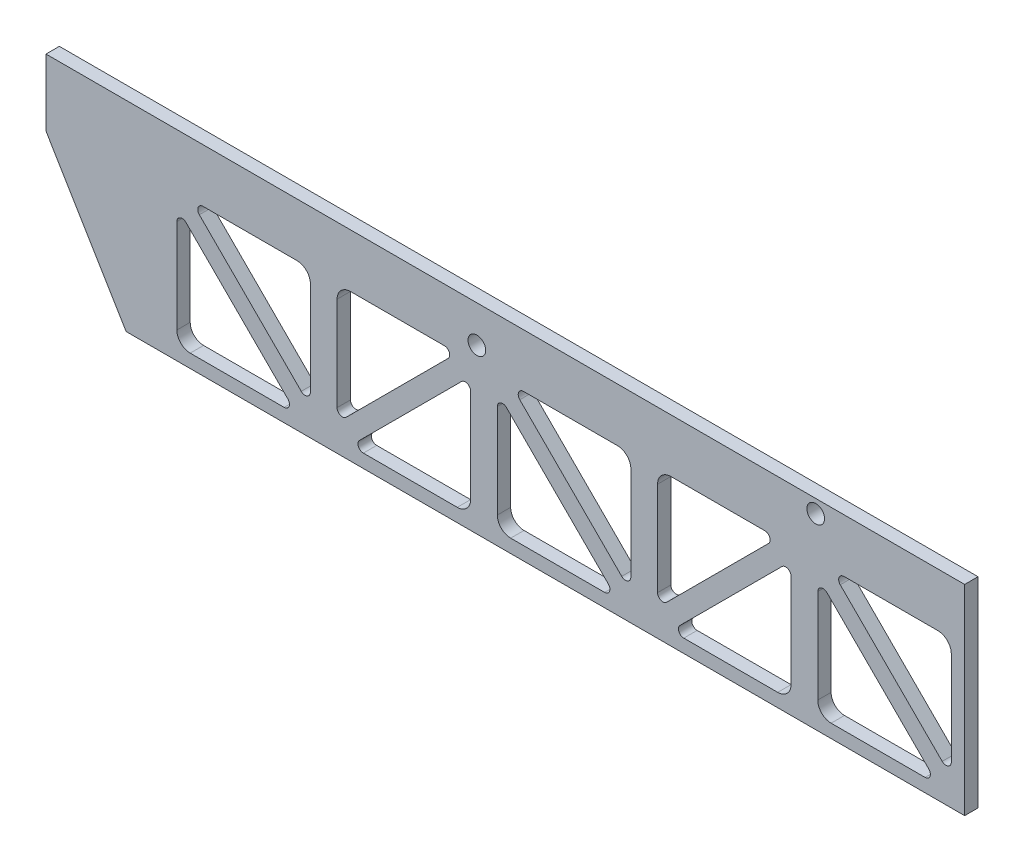
SolidWorks part; units mm, degrees
material "Balsa"
ref_plane "Front Plane" through (0, 0, 0) normal (0, 0, 1) x (1, 0, 0)
ref_plane "Top Plane" through (0, 0, 0) normal (0, 1, 0) x (1, 0, 0)
ref_plane "Right Plane" through (0, 0, 0) normal (1, 0, 0) x (0, 0, -1)
sketch "Model" plane through (0, 0, 0) normal (0, 0, 1) x (1, 0, 0)
  line L0 (-74.8917, 84.8995) -> (-66.8907, 84.8995)
  line L1 (-74.8917, 92.9005) -> (-74.8917, 84.8995)
  line L2 (-66.8907, 92.9005) -> (-74.8917, 92.9005)
  line L3 (-66.8907, 84.8995) -> (-66.8907, 92.9005)
  line L4 (-235.9382, 73.8654) -> (-227.9376, 73.7809)
  line L5 (-235.8537, 81.866) -> (-235.9382, 73.8654)
  line L6 (-227.8532, 81.7815) -> (-235.8537, 81.866)
  line L7 (-227.9376, 73.7809) -> (-227.8532, 81.7815)
  line L8 (-171.2321, 6.35) -> (-215.9, 6.35)
  line L9 (-222.25, 57.3679) -> (-222.25, 12.7)
  line L10 (-217.9139, 59.1639) -> (-169.4361, 10.6861)
  line L11 (-234.95, 57.3679) -> (-234.95, 12.7)
  line L12 (-241.3, 6.35) -> (-285.9679, 6.35)
  line L13 (-239.2861, 59.1639) -> (-287.7639, 10.6861)
  line L14 (-294.1139, 17.0361) -> (-245.6361, 65.5139)
  line L15 (-298.45, 63.5) -> (-298.45, 18.8321)
  line L16 (-247.4321, 69.85) -> (-292.1, 69.85)
  line L17 (-323.6321, 6.35) -> (-368.3, 6.35)
  line L18 (-374.65, 57.3679) -> (-374.65, 12.7)
  line L19 (-370.3139, 59.1639) -> (-321.8361, 10.6861)
  line L20 (-18.8321, 6.35) -> (-63.5, 6.35)
  line L21 (-69.85, 57.3679) -> (-69.85, 12.7)
  line L22 (-17.0361, 10.6861) -> (-65.5139, 59.1639)
  line L23 (-82.55, 57.3679) -> (-82.55, 12.7)
  line L24 (-88.9, 6.35) -> (-133.5679, 6.35)
  line L25 (-86.8861, 59.1639) -> (-135.3639, 10.6861)
  line L26 (-93.2361, 65.5139) -> (-141.7139, 17.0361)
  line L27 (-146.05, 63.5) -> (-146.05, 18.8321)
  line L28 (-95.0321, 69.85) -> (-139.7, 69.85)
  line L29 (-163.0861, 17.0361) -> (-211.5639, 65.5139)
  line L30 (-165.1, 69.85) -> (-209.7679, 69.85)
  line L31 (-158.75, 63.5) -> (-158.75, 18.8321)
  line L32 (-315.4861, 17.0361) -> (-363.9639, 65.5139)
  line L33 (-317.5, 69.85) -> (-362.1679, 69.85)
  line L34 (-311.15, 63.5) -> (-311.15, 18.8321)
  line L35 (-398.78, 0) -> (-436.88, 63.5)
  line L36 (0, 0) -> (-398.78, 0)
  line L37 (0, 0) -> (0, 95.25)
  line L38 (0, 95.25) -> (-436.88, 95.25)
  line L39 (-436.88, 63.5) -> (-436.88, 95.25)
  line L40 (-6.35, 63.5) -> (-6.35, 18.8321)
  line L41 (-59.1639, 65.5139) -> (-10.6861, 17.0361)
  line L42 (-12.7, 69.85) -> (-57.3679, 69.85)
  arc A0 (-222.25, 12.7) -> (-215.9, 6.35) centre (-215.9, 12.7) ccw
  arc A1 (-217.9139, 59.1639) -> (-222.25, 57.3679) centre (-219.71, 57.3679) ccw
  arc A2 (-171.2321, 6.35) -> (-169.4361, 10.6861) centre (-171.2321, 8.89) ccw
  arc A3 (-234.95, 57.3679) -> (-239.2861, 59.1639) centre (-237.49, 57.3679) ccw
  arc A4 (-241.3, 6.35) -> (-234.95, 12.7) centre (-241.3, 12.7) ccw
  arc A5 (-287.7639, 10.6861) -> (-285.9679, 6.35) centre (-285.9679, 8.89) ccw
  arc A6 (-245.6361, 65.5139) -> (-247.4321, 69.85) centre (-247.4321, 67.31) ccw
  arc A7 (-298.45, 18.8321) -> (-294.1139, 17.0361) centre (-295.91, 18.8321) ccw
  arc A8 (-292.1, 69.85) -> (-298.45, 63.5) centre (-292.1, 63.5) ccw
  arc A9 (-323.6321, 6.35) -> (-321.8361, 10.6861) centre (-323.6321, 8.89) ccw
  arc A10 (-374.65, 12.7) -> (-368.3, 6.35) centre (-368.3, 12.7) ccw
  arc A11 (-370.3139, 59.1639) -> (-374.65, 57.3679) centre (-372.11, 57.3679) ccw
  arc A12 (-69.85, 12.7) -> (-63.5, 6.35) centre (-63.5, 12.7) ccw
  arc A13 (-65.5139, 59.1639) -> (-69.85, 57.3679) centre (-67.31, 57.3679) ccw
  arc A14 (-18.8321, 6.35) -> (-17.0361, 10.6861) centre (-18.8321, 8.89) ccw
  arc A15 (-82.55, 57.3679) -> (-86.8861, 59.1639) centre (-85.09, 57.3679) ccw
  arc A16 (-88.9, 6.35) -> (-82.55, 12.7) centre (-88.9, 12.7) ccw
  arc A17 (-135.3639, 10.6861) -> (-133.5679, 6.35) centre (-133.5679, 8.89) ccw
  arc A18 (-93.2361, 65.5139) -> (-95.0321, 69.85) centre (-95.0321, 67.31) ccw
  arc A19 (-146.05, 18.8321) -> (-141.7139, 17.0361) centre (-143.51, 18.8321) ccw
  arc A20 (-139.7, 69.85) -> (-146.05, 63.5) centre (-139.7, 63.5) ccw
  arc A21 (-163.0861, 17.0361) -> (-158.75, 18.8321) centre (-161.29, 18.8321) ccw
  arc A22 (-209.7679, 69.85) -> (-211.5639, 65.5139) centre (-209.7679, 67.31) ccw
  arc A23 (-158.75, 63.5) -> (-165.1, 69.85) centre (-165.1, 63.5) ccw
  arc A24 (-362.1679, 69.85) -> (-363.9639, 65.5139) centre (-362.1679, 67.31) ccw
  arc A25 (-311.15, 63.5) -> (-317.5, 69.85) centre (-317.5, 63.5) ccw
  arc A26 (-315.4861, 17.0361) -> (-311.15, 18.8321) centre (-313.69, 18.8321) ccw
  arc A27 (-10.6861, 17.0361) -> (-6.35, 18.8321) centre (-8.89, 18.8321) ccw
  arc A28 (-57.3679, 69.85) -> (-59.1639, 65.5139) centre (-57.3679, 67.31) ccw
  arc A29 (-6.35, 63.5) -> (-12.7, 69.85) centre (-12.7, 63.5) ccw
  dimension "D1" = 95.25
extrude "Boss-Extrude1" add sketch "Model" along normal blind 6.35
sketch "Sketch1" plane through (0, 0, 6.35) normal (0, 0, 1) x (1, 0, 0)
  line L0 (-227.8532, 81.7815) -> (-235.8537, 81.866) construction
  line L1 (-236.1635, 81.9643) -> (-227.7561, 81.9643)
  line L2 (-236.1635, 81.9643) -> (-236.1635, 73.5569)
  line L3 (-236.1635, 73.5569) -> (-227.7561, 73.5569)
  line L4 (-227.7561, 81.9643) -> (-227.7561, 73.5569)
  line L5 (-227.9376, 73.7809) -> (-227.8532, 81.7815) construction
  line L6 (-74.8917, 92.9005) -> (-74.8917, 84.8995) construction
  line L7 (-75.0314, 93.1672) -> (-66.624, 93.1672)
  line L8 (-75.0314, 93.1672) -> (-75.0314, 84.7598)
  line L9 (-75.0314, 84.7598) -> (-66.624, 84.7598)
  line L10 (-66.624, 93.1672) -> (-66.624, 84.7598)
  line L11 (-74.8917, 84.8995) -> (-66.8907, 84.8995) construction
  circle A0 centre (-231.9598, 77.7606) radius 4.2037
  circle A1 centre (-70.8277, 88.9635) radius 4.2037
  point P8 (-232.6111, 77.8657)
  point P9 (0, 0)
  point P20 (-69.052, 100.687)
  point P22 (-68.3812, 97.0817)
  dimension "D2" = 8.4074
  dimension "D6" = 8.4074
  dimension "D1" = 4.064
  dimension "D3" = 4.064
  dimension "D4" = 4.064
  dimension "D5" = 4.064
extrude "Boss-Extrude2" add sketch "Sketch1" against normal up to surface (6.35 mm away) contours A0 L1 L2 | A0 L4 L1 | A0 L3 L4 | A0 L2 L3 | A1 L7 L8 | A1 L10 L7 | A1 L9 L10 | A1 L8 L9 region at (-235.2246, 81.0254, 6.35) region at (-228.6951, 81.0254, 6.35) region at (-235.2246, 74.4959, 6.35) region at (-228.6951, 74.4959, 6.35) region at (-74.0924, 92.2282, 6.35) region at (-67.563, 92.2282, 6.35) region at (-74.0924, 85.6988, 6.35) region at (-67.563, 85.6988, 6.35) up to face at (-254.508, 50.8, 0)
extrude "Cut-Extrude1" cut sketch "Sketch1<3>" against normal up to surface (6.35 mm away) contours A0 | A1 | A1 region at (-231.9598, 77.7606, 6.35) region at (-70.8277, 88.9635, 6.35) up to face at (-70.8806, 88.9106, 0)
sketch "Sketch1<3>" plane through (0, 0, 6.35) normal (0, 0, 1) x (1, 0, 0) same geometry as "Sketch1"
equation "\"thick\"=0.25"
equation "\"D1@Boss-Extrude1\"=\"thick\""
